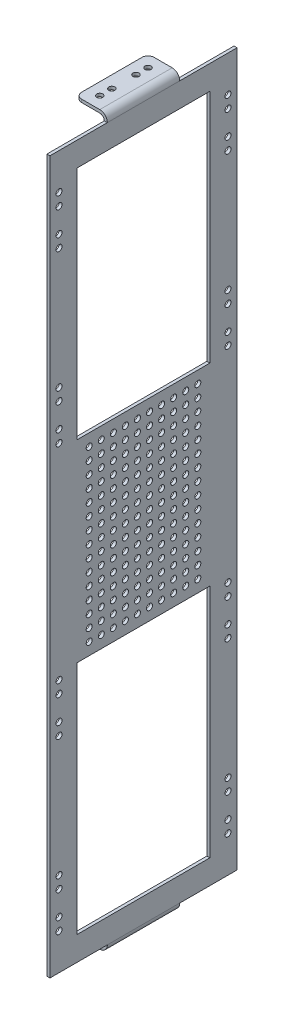
SolidWorks part; units mm, degrees
material "6061-T6 (SS)"
ref_plane "Front Plane" through (0, 0, 0) normal (0, 0, 1) x (1, 0, 0)
ref_plane "Top Plane" through (0, 0, 0) normal (0, 1, 0) x (1, 0, 0)
ref_plane "Right Plane" through (0, 0, 0) normal (1, 0, 0) x (0, 0, -1)
sketch "Sketch1" plane through (0, 0, 0) normal (1, 0, 0) x (0, 0, -1)
  line L1 (0, 0) -> (95.25, 0)
  line L2 (0, 0) -> (0, 374.65)
  line L3 (0, 374.65) -> (95.25, 374.65)
  line L4 (95.25, 0) -> (95.25, 374.65)
  dimension "D1" = 95.25
  dimension "D2" = 374.65
extrude "MainPlateExtrude" add sketch "Sketch1" along normal blind 1.5875
sketch "Sketch4" plane through (0, 0, 0) normal (-1, 0, 0) x (0, 0, 1)
  line L0 (-82.55, 12.7) -> (-82.55, 361.95)
  line L1 (-95.25, 0) -> (0, 0) construction
  line L2 (-95.25, 0) -> (-95.25, 374.65) construction
  line L3 (-95.25, 374.65) -> (0, 374.65) construction
  line L4 (0, 0) -> (0, 374.65) construction
  line L5 (-82.55, 361.95) -> (-12.7, 361.95)
  line L6 (-12.7, 12.7) -> (-12.7, 361.95)
  line L7 (-82.55, 12.7) -> (-12.7, 12.7)
  dimension "D1" = 12.7
extrude "WallOpening" cut sketch "Sketch4" against normal blind 1.5875
sketch "Sketch5" plane through (0, 0, 0) normal (-1, 0, 0) x (0, 0, 1)
  line L0 (-95.25, 187.325) -> (0, 187.325) construction
  line L1 (-95.25, 0) -> (-95.25, 374.65) construction
  line L2 (0, 374.65) -> (0, 0) construction
  line L3 (-82.55, 361.95) -> (-82.55, 12.7) construction
  line L4 (-82.55, 238.125) -> (-12.7, 238.125)
  line L5 (-82.55, 238.125) -> (-82.55, 136.525)
  line L6 (-82.55, 136.525) -> (-12.7, 136.525)
  line L7 (-12.7, 238.125) -> (-12.7, 136.525)
  line L8 (-12.7, 12.7) -> (-12.7, 361.95) construction
  circle A0 centre (-76.2, 231.775) radius 1.5875
  circle A1 centre (-69.85, 231.775) radius 1.5875
  circle A2 centre (-63.5, 231.775) radius 1.5875
  circle A3 centre (-57.15, 231.775) radius 1.5875
  circle A4 centre (-50.8, 231.775) radius 1.5875
  circle A5 centre (-44.45, 231.775) radius 1.5875
  circle A6 centre (-38.1, 231.775) radius 1.5875
  circle A7 centre (-31.75, 231.775) radius 1.5875
  circle A8 centre (-25.4, 231.775) radius 1.5875
  circle A9 centre (-19.05, 231.775) radius 1.5875
  circle A10 centre (-69.85, 225.425) radius 1.5875
  circle A11 centre (-63.5, 225.425) radius 1.5875
  circle A12 centre (-57.15, 225.425) radius 1.5875
  circle A13 centre (-50.8, 225.425) radius 1.5875
  circle A14 centre (-44.45, 225.425) radius 1.5875
  circle A15 centre (-38.1, 225.425) radius 1.5875
  circle A16 centre (-31.75, 225.425) radius 1.5875
  circle A17 centre (-25.4, 225.425) radius 1.5875
  circle A18 centre (-19.05, 225.425) radius 1.5875
  circle A19 centre (-69.85, 219.075) radius 1.5875
  circle A20 centre (-63.5, 219.075) radius 1.5875
  circle A21 centre (-57.15, 219.075) radius 1.5875
  circle A22 centre (-50.8, 219.075) radius 1.5875
  circle A23 centre (-44.45, 219.075) radius 1.5875
  circle A24 centre (-38.1, 219.075) radius 1.5875
  circle A25 centre (-31.75, 219.075) radius 1.5875
  circle A26 centre (-25.4, 219.075) radius 1.5875
  circle A27 centre (-19.05, 219.075) radius 1.5875
  circle A28 centre (-69.85, 212.725) radius 1.5875
  circle A29 centre (-63.5, 212.725) radius 1.5875
  circle A30 centre (-57.15, 212.725) radius 1.5875
  circle A31 centre (-50.8, 212.725) radius 1.5875
  circle A32 centre (-44.45, 212.725) radius 1.5875
  circle A33 centre (-38.1, 212.725) radius 1.5875
  circle A34 centre (-31.75, 212.725) radius 1.5875
  circle A35 centre (-25.4, 212.725) radius 1.5875
  circle A36 centre (-19.05, 212.725) radius 1.5875
  circle A37 centre (-69.85, 206.375) radius 1.5875
  circle A38 centre (-63.5, 206.375) radius 1.5875
  circle A39 centre (-57.15, 206.375) radius 1.5875
  circle A40 centre (-50.8, 206.375) radius 1.5875
  circle A41 centre (-44.45, 206.375) radius 1.5875
  circle A42 centre (-38.1, 206.375) radius 1.5875
  circle A43 centre (-31.75, 206.375) radius 1.5875
  circle A44 centre (-25.4, 206.375) radius 1.5875
  circle A45 centre (-19.05, 206.375) radius 1.5875
  circle A46 centre (-69.85, 200.025) radius 1.5875
  circle A47 centre (-63.5, 200.025) radius 1.5875
  circle A48 centre (-57.15, 200.025) radius 1.5875
  circle A49 centre (-50.8, 200.025) radius 1.5875
  circle A50 centre (-44.45, 200.025) radius 1.5875
  circle A51 centre (-38.1, 200.025) radius 1.5875
  circle A52 centre (-31.75, 200.025) radius 1.5875
  circle A53 centre (-25.4, 200.025) radius 1.5875
  circle A54 centre (-19.05, 200.025) radius 1.5875
  circle A55 centre (-69.85, 193.675) radius 1.5875
  circle A56 centre (-63.5, 193.675) radius 1.5875
  circle A57 centre (-57.15, 193.675) radius 1.5875
  circle A58 centre (-50.8, 193.675) radius 1.5875
  circle A59 centre (-44.45, 193.675) radius 1.5875
  circle A60 centre (-38.1, 193.675) radius 1.5875
  circle A61 centre (-31.75, 193.675) radius 1.5875
  circle A62 centre (-25.4, 193.675) radius 1.5875
  circle A63 centre (-19.05, 193.675) radius 1.5875
  circle A64 centre (-69.85, 187.325) radius 1.5875
  circle A65 centre (-63.5, 187.325) radius 1.5875
  circle A66 centre (-57.15, 187.325) radius 1.5875
  circle A67 centre (-50.8, 187.325) radius 1.5875
  circle A68 centre (-44.45, 187.325) radius 1.5875
  circle A69 centre (-38.1, 187.325) radius 1.5875
  circle A70 centre (-31.75, 187.325) radius 1.5875
  circle A71 centre (-25.4, 187.325) radius 1.5875
  circle A72 centre (-19.05, 187.325) radius 1.5875
  circle A73 centre (-69.85, 180.975) radius 1.5875
  circle A74 centre (-63.5, 180.975) radius 1.5875
  circle A75 centre (-57.15, 180.975) radius 1.5875
  circle A76 centre (-50.8, 180.975) radius 1.5875
  circle A77 centre (-44.45, 180.975) radius 1.5875
  circle A78 centre (-38.1, 180.975) radius 1.5875
  circle A79 centre (-31.75, 180.975) radius 1.5875
  circle A80 centre (-25.4, 180.975) radius 1.5875
  circle A81 centre (-19.05, 180.975) radius 1.5875
  circle A82 centre (-69.85, 174.625) radius 1.5875
  circle A83 centre (-63.5, 174.625) radius 1.5875
  circle A84 centre (-57.15, 174.625) radius 1.5875
  circle A85 centre (-50.8, 174.625) radius 1.5875
  circle A86 centre (-44.45, 174.625) radius 1.5875
  circle A87 centre (-38.1, 174.625) radius 1.5875
  circle A88 centre (-31.75, 174.625) radius 1.5875
  circle A89 centre (-25.4, 174.625) radius 1.5875
  circle A90 centre (-19.05, 174.625) radius 1.5875
  circle A91 centre (-69.85, 168.275) radius 1.5875
  circle A92 centre (-63.5, 168.275) radius 1.5875
  circle A93 centre (-57.15, 168.275) radius 1.5875
  circle A94 centre (-50.8, 168.275) radius 1.5875
  circle A95 centre (-44.45, 168.275) radius 1.5875
  circle A96 centre (-38.1, 168.275) radius 1.5875
  circle A97 centre (-31.75, 168.275) radius 1.5875
  circle A98 centre (-25.4, 168.275) radius 1.5875
  circle A99 centre (-19.05, 168.275) radius 1.5875
  circle A100 centre (-69.85, 161.925) radius 1.5875
  circle A101 centre (-63.5, 161.925) radius 1.5875
  circle A102 centre (-57.15, 161.925) radius 1.5875
  circle A103 centre (-50.8, 161.925) radius 1.5875
  circle A104 centre (-44.45, 161.925) radius 1.5875
  circle A105 centre (-38.1, 161.925) radius 1.5875
  circle A106 centre (-31.75, 161.925) radius 1.5875
  circle A107 centre (-25.4, 161.925) radius 1.5875
  circle A108 centre (-19.05, 161.925) radius 1.5875
  circle A109 centre (-69.85, 155.575) radius 1.5875
  circle A110 centre (-63.5, 155.575) radius 1.5875
  circle A111 centre (-57.15, 155.575) radius 1.5875
  circle A112 centre (-50.8, 155.575) radius 1.5875
  circle A113 centre (-44.45, 155.575) radius 1.5875
  circle A114 centre (-38.1, 155.575) radius 1.5875
  circle A115 centre (-31.75, 155.575) radius 1.5875
  circle A116 centre (-25.4, 155.575) radius 1.5875
  circle A117 centre (-19.05, 155.575) radius 1.5875
  circle A118 centre (-69.85, 149.225) radius 1.5875
  circle A119 centre (-63.5, 149.225) radius 1.5875
  circle A120 centre (-57.15, 149.225) radius 1.5875
  circle A121 centre (-50.8, 149.225) radius 1.5875
  circle A122 centre (-44.45, 149.225) radius 1.5875
  circle A123 centre (-38.1, 149.225) radius 1.5875
  circle A124 centre (-31.75, 149.225) radius 1.5875
  circle A125 centre (-25.4, 149.225) radius 1.5875
  circle A126 centre (-19.05, 149.225) radius 1.5875
  circle A127 centre (-69.85, 142.875) radius 1.5875
  circle A128 centre (-63.5, 142.875) radius 1.5875
  circle A129 centre (-57.15, 142.875) radius 1.5875
  circle A130 centre (-50.8, 142.875) radius 1.5875
  circle A131 centre (-44.45, 142.875) radius 1.5875
  circle A132 centre (-38.1, 142.875) radius 1.5875
  circle A133 centre (-31.75, 142.875) radius 1.5875
  circle A134 centre (-25.4, 142.875) radius 1.5875
  circle A135 centre (-19.05, 142.875) radius 1.5875
  circle A136 centre (-76.2, 225.425) radius 1.5875
  circle A137 centre (-76.2, 219.075) radius 1.5875
  circle A138 centre (-76.2, 212.725) radius 1.5875
  circle A139 centre (-76.2, 206.375) radius 1.5875
  circle A140 centre (-76.2, 200.025) radius 1.5875
  circle A141 centre (-76.2, 193.675) radius 1.5875
  circle A142 centre (-76.2, 187.325) radius 1.5875
  circle A143 centre (-76.2, 180.975) radius 1.5875
  circle A144 centre (-76.2, 174.625) radius 1.5875
  circle A145 centre (-76.2, 168.275) radius 1.5875
  circle A146 centre (-76.2, 161.925) radius 1.5875
  circle A147 centre (-76.2, 155.575) radius 1.5875
  circle A148 centre (-76.2, 149.225) radius 1.5875
  circle A149 centre (-76.2, 142.875) radius 1.5875
  dimension "D3" = 3.175
  dimension "D1" = 50.8
  dimension "D2" = 50.8
  dimension "D4" = 6.35
  dimension "D5" = 6.35
  dimension "D6" = 10
  dimension "D7" = 15
extrude "AntennaeMount" add sketch "Sketch5" against normal blind 1.5875
ref_plane "Plane1" through (0, 0, -47.625) normal (0, 0, -1) x (-1, 0, 0)
sketch "Sketch7" plane through (0, 0, -47.625) normal (0, 0, -1) x (-1, 0, 0)
  line L0 (-1.5875, 374.65) -> (0, 374.65) construction
  line L1 (-1.5875, 374.65) -> (0, 374.65) construction
  line L2 (2.3813, 377.0312) -> (2.3813, 374.65) construction
  line L3 (2.3813, 374.65) -> (-1.5875, 374.65) construction
  line L4 (0, 374.65) -> (-1.5875, 374.65)
  line L6 (2.3813, 378.6187) -> (15.0812, 378.6187)
  line L8 (2.3813, 377.0312) -> (15.0812, 377.0312)
  line L9 (15.0812, 378.6187) -> (15.0812, 377.0312)
  arc A0 (-1.5875, 374.65) -> (2.3813, 378.6187) centre (2.3813, 374.65) cw
  arc A1 (0, 374.65) -> (2.3813, 377.0312) centre (2.3813, 374.65) cw
  dimension "D1" = 3.9688
  dimension "D3" = 2.3813
  dimension "D2" = 1.5875
  dimension "D4" = 12.7
extrude "Boss-Extrude1" add sketch "Sketch7" along normal blind 19.05
mirror "Mirror1" about plane through (0, 0, -47.625) normal (0, 0, -1) of "Boss-Extrude1"
ref_plane "Plane2" through (0, 187.325, 0) normal (0, 1, 0) x (1, 0, 0)
mirror "Mirror2" about plane through (0, 187.325, 0) normal (0, 1, 0) of "Mirror1", "Boss-Extrude1"
fillet "Fillet1" radius 3.175 4 edges at (-15.0812, 377.825, -28.575) (-15.0812, 377.825, -66.675) (-15.0812, -3.175, -28.575) (-15.0812, -3.175, -66.675)
sketch "Sketch8" plane through (0, 378.6187, 0) normal (0, 1, 0) x (1, 0, 0)
  line L0 (-15.0812, 47.625) -> (-2.3813, 47.625) construction
  line L1 (-15.0812, 63.5) -> (-15.0812, 31.75) construction
  line L2 (-2.3813, 66.675) -> (-2.3813, 28.575) construction
  line L3 (-8.7313, 47.625) -> (-8.7313, 66.675) construction
  line L4 (-11.9062, 66.675) -> (-2.3813, 66.675) construction
  line L5 (-8.7313, 47.625) -> (-8.7313, 28.575) construction
  line L6 (-11.9062, 28.575) -> (-2.3813, 28.575) construction
  circle A0 centre (-8.7313, 34.925) radius 1.5875
  circle A1 centre (-8.7313, 41.275) radius 1.5875
  circle A2 centre (-8.7313, 53.975) radius 1.5875
  circle A3 centre (-8.7313, 60.325) radius 1.5875
  dimension "D1" = 3.175
  dimension "D2" = 3.175
  dimension "D3" = 3.175
  dimension "D4" = 3.175
  dimension "D5" = 6.35
  dimension "D6" = 6.35
  dimension "D7" = 6.35
  dimension "D8" = 6.35
extrude "Cut-Extrude1" cut sketch "Sketch8" against normal blind 382.905
sketch "Sketch9" plane through (1.5875, 0, 0) normal (1, 0, 0) x (0, 0, -1)
  line L0 (12.7, 361.95) -> (0, 361.95) construction
  line L1 (0, 374.65) -> (0, 0) construction
  line L2 (6.35, 361.95) -> (6.35, 374.65) construction
  line L3 (28.575, 374.65) -> (0, 374.65) construction
  line L4 (6.35, 361.95) -> (6.35, 0) construction
  line L5 (0, 0) -> (28.575, 0) construction
  line L6 (3.175, 355.6) -> (3.175, 349.25) construction
  line L7 (3.175, 349.25) -> (3.175, 336.55) construction
  line L8 (3.175, 336.55) -> (3.175, 330.2) construction
  line L9 (3.175, 330.2) -> (3.175, 266.7) construction
  line L10 (3.175, 241.3) -> (3.175, 133.35) construction
  line L11 (3.175, 107.95) -> (3.175, 44.45) construction
  circle A0 centre (3.175, 355.6) radius 1.5875
  circle A1 centre (3.175, 349.25) radius 1.5875
  circle A2 centre (3.175, 336.55) radius 1.5875
  circle A3 centre (3.175, 330.2) radius 1.5875
  circle A4 centre (3.175, 247.65) radius 1.5875
  circle A5 centre (3.175, 241.3) radius 1.5875
  circle A6 centre (3.175, 266.7) radius 1.5875
  circle A7 centre (3.175, 260.35) radius 1.5875
  circle A8 centre (3.175, 127) radius 1.5875
  circle A9 centre (3.175, 133.35) radius 1.5875
  circle A10 centre (3.175, 107.95) radius 1.5875
  circle A11 centre (3.175, 114.3) radius 1.5875
  circle A12 centre (3.175, 25.4) radius 1.5875
  circle A13 centre (3.175, 19.05) radius 1.5875
  circle A14 centre (3.175, 38.1) radius 1.5875
  circle A15 centre (3.175, 44.45) radius 1.5875
  dimension "D1" = 19.05
  dimension "D3" = 3.175
  dimension "D4" = 3.175
  dimension "D9" = 63.5
  dimension "D2" = 3.175
  dimension "D5" = 6.35
  dimension "D6" = 3.175
  dimension "D7" = 12.7
  dimension "D8" = 6.35
  dimension "D10" = 107.95
  dimension "D11" = 6.35
  dimension "D12" = 12.7
  dimension "D13" = 6.35
  dimension "D14" = 6.35
  dimension "D15" = 12.7
  dimension "D16" = 6.35
  dimension "D17" = 63.5
extrude "Cut-Extrude2" cut sketch "Sketch9" against normal blind 25.4
ref_plane "Plane3" through (0, 0, -47.625) normal (0, 0, 1) x (1, 0, 0)
mirror "Mirror3" about plane through (0, 0, -47.625) normal (0, 0, 1) of "Cut-Extrude2"
sketch "Sketch10" plane through (0, 0, 0) normal (0, 0, 1) x (1, 0, 0)
  line L1 (0, 374.65) -> (1.5875, 374.65)
  line L2 (0, 374.65) -> (0, 0)
  line L3 (0, 0) -> (1.5875, 0)
  line L4 (1.5875, 374.65) -> (1.5875, 0)
extrude "Boss-Extrude2" add sketch "Sketch10" along normal blind 1.5875
mirror "Mirror4" about plane through (0, 0, -47.625) normal (0, 0, 1) of "Boss-Extrude2"
